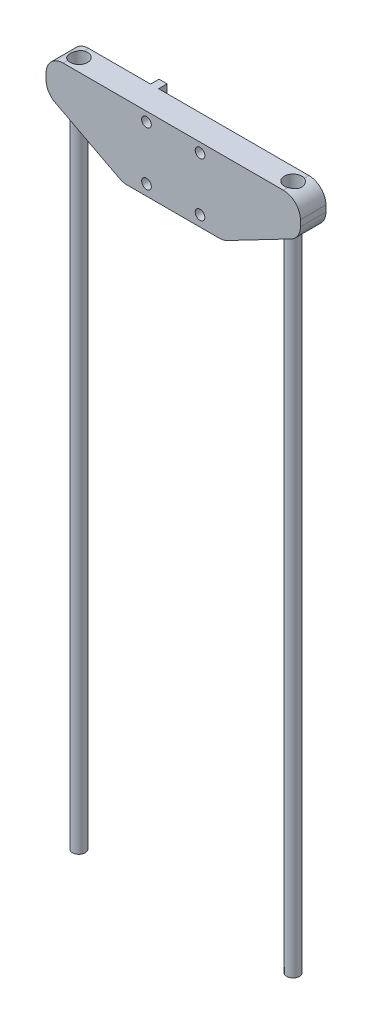
SolidWorks part; units mm, degrees
other "Markup2"
sketch "Sketch8"
other "Markup3"
sketch "Sketch15"
ref_plane "Front Plane" through (0, 0, 0) normal (0, 0, 1) x (1, 0, 0)
ref_plane "Top Plane" through (0, 0, 0) normal (0, 1, 0) x (1, 0, 0)
ref_plane "Right Plane" through (0, 0, 0) normal (1, 0, 0) x (0, 0, -1)
sketch "Sketch2" plane through (0, 0, 0) normal (0, 0, 1) x (1, 0, 0)
  line L0 (-40, 0) -> (-40, -243.6) construction
  line L1 (40, 0) -> (40, -243.6) construction
  line L2 (0, 48.6067) -> (0, -93.2297) construction
  line L3 (-47.5, 12.5) -> (-47.5, 0)
  line L4 (-47.5, 0) -> (-18.75, -15)
  line L5 (-18.75, -15) -> (18.75, -15)
  line L6 (18.75, -15) -> (47.5, 0)
  line L7 (-47.5, 12.5) -> (47.5, 12.5)
  line L8 (47.5, 12.5) -> (47.5, 0)
  line L10 (-42.3812, 0) -> (-37.6188, 0)
  line L11 (-42.3812, 0) -> (-42.3812, -243.6)
  line L12 (-42.3812, -243.6) -> (-37.6187, -243.6)
  line L13 (-37.6188, 0) -> (-37.6187, -243.6)
  line L14 (-10, 9) -> (10, 9) construction
  line L15 (-10, 9) -> (-10, -11) construction
  line L16 (-10, -11) -> (10, -11) construction
  line L17 (10, 9) -> (10, -11) construction
  line L18 (37.6188, -243.6) -> (42.3813, -243.6)
  line L19 (37.6188, -243.6) -> (37.6188, 0)
  line L20 (37.6188, 0) -> (42.3812, 0)
  line L21 (42.3813, -243.6) -> (42.3812, 0)
  dimension "D1" = 80
  dimension "D3" = 4.7625
  dimension "D4" = 20
  dimension "D5" = 20
  dimension "D6" = 228.6
  dimension "12.5" = 12.5
  dimension "D8" = 15
  dimension "D9" = 4
  dimension "D10" = 12.5
  dimension "D11" = 95
  dimension "D12" = 37.5
sketch "Sketch9" plane through (0, 0, 0) normal (0, 1, 0) x (1, 0, 0)
  line L0 (-40, 0) -> (-35, 0) construction
  line L2 (-40, 2.3812) -> (-35, 2.3812)
  line L3 (-40, -2.3812) -> (-35, -2.3812)
  line L4 (0, 20.7896) -> (0, -26.7229) construction
  line L5 (40, 0) -> (35, 0) construction
  line L6 (40, 2.3813) -> (35, 2.3813)
  line L7 (40, -2.3813) -> (35, -2.3813)
  line L8 (-37.5, 2.3812) -> (-37.5, -2.3812) construction
  line L9 (-42.3812, 0) -> (-37.6187, 0) construction
  line L10 (37.5, 2.3813) -> (37.5, -2.3813) construction
  arc A0 (-40, 2.3812) -> (-40, -2.3812) centre (-40, 0) ccw
  arc A1 (-35, -2.3812) -> (-35, 2.3812) centre (-35, 0) ccw
  arc A2 (40, 2.3813) -> (40, -2.3813) centre (40, 0) cw
  arc A3 (35, -2.3813) -> (35, 2.3813) centre (35, 0) cw
  circle A4 centre (-40, 0) radius 1.5
  circle A5 centre (40, 0) radius 1.5
  point P5 (-37.5, 0)
  point P15 (37.5, 0)
  dimension "D1" = 5
  dimension "D3" = 3
  dimension "D2" = 4.7625
sketch "Sketch3" plane through (0, 0, 0) normal (0, 0, 1) x (1, 0, 0)
  line L0 (-47.5, 12.5) -> (-47.5, 0) construction
  line L1 (-47.5, 0) -> (-18.75, -15) construction
  line L2 (-18.75, -15) -> (18.75, -15) construction
  line L3 (18.75, -15) -> (47.5, 0) construction
  line L4 (47.5, 12.5) -> (47.5, 0) construction
  line L5 (-47.5, 12.5) -> (47.5, 12.5) construction
  line L6 (-47.5, 12.5) -> (-47.5, 0)
  line L7 (-47.5, 0) -> (-18.75, -15)
  line L8 (-18.75, -15) -> (18.75, -15)
  line L9 (18.75, -15) -> (47.5, 0)
  line L10 (47.5, 12.5) -> (47.5, 0)
  line L11 (-47.5, 12.5) -> (47.5, 12.5)
extrude "Boss-Extrude1" add sketch "Sketch3" along normal mid plane 9.525
sketch "Sketch10" plane through (0, 0, 0) normal (0, 1, 0) x (1, 0, 0)
  line L0 (40, 2.3813) -> (35, 2.3813) construction
  line L1 (40, -2.3813) -> (35, -2.3813) construction
  line L2 (-40, 2.3812) -> (-35, 2.3812) construction
  line L3 (-40, -2.3812) -> (-35, -2.3812) construction
  line L4 (40, 2.3813) -> (35, 2.3813)
  line L5 (40, -2.3813) -> (35, -2.3813)
  line L6 (-40, 2.3812) -> (-35, 2.3812)
  line L7 (-40, -2.3812) -> (-35, -2.3812)
  arc A0 (35, 2.3813) -> (35, -2.3813) centre (35, 0) ccw construction
  arc A1 (40, -2.3813) -> (40, 2.3813) centre (40, 0) ccw construction
  arc A2 (-35, -2.3812) -> (-35, 2.3812) centre (-35, 0) ccw construction
  arc A3 (-40, 2.3812) -> (-40, -2.3812) centre (-40, 0) ccw construction
  arc A4 (35, 2.3813) -> (35, -2.3813) centre (35, 0) ccw
  arc A5 (40, -2.3813) -> (40, 2.3813) centre (40, 0) ccw
  arc A6 (-35, -2.3812) -> (-35, 2.3812) centre (-35, 0) ccw
  arc A7 (-40, 2.3812) -> (-40, -2.3812) centre (-40, 0) ccw
extrude "Cut-Extrude1" cut sketch "Sketch10" against normal blind 10
sketch "Sketch4" plane through (0, 0, 0) normal (0, 0, 1) x (1, 0, 0)
  line L0 (40, 0) -> (40, -243.6) construction
  line L1 (-40, 0) -> (-40, -243.6) construction
  line L2 (-42.3812, 0) -> (-42.3812, -243.6) construction
  line L3 (-42.3812, -243.6) -> (-37.6187, -243.6) construction
  line L4 (-37.6188, 0) -> (-37.6187, -243.6) construction
  line L5 (-42.3812, 0) -> (-37.6188, 0) construction
  line L6 (40, 0) -> (40, -243.6)
  line L7 (-40, 0) -> (-40, -243.6)
  line L8 (-42.3812, 0) -> (-42.3812, -243.6)
  line L9 (-42.3812, -243.6) -> (-40, -243.6)
  line L10 (-37.6188, 0) -> (-37.6187, -243.6) construction
  line L11 (-42.3812, 0) -> (-40, 0)
  line L12 (-40, -243.6) -> (-40, -275.6996) construction
  line L13 (-40, -243.6) -> (-37.6187, -243.6) construction
  line L14 (-40, 0) -> (-37.6188, 0) construction
  line L15 (40, -243.6) -> (40, -281.3243) construction
  line L16 (37.6188, -243.6) -> (42.3813, -243.6)
  line L17 (37.6188, -243.6) -> (37.6188, 0)
  line L18 (37.6188, 0) -> (42.3812, 0)
  line L19 (42.3813, -243.6) -> (42.3812, 0)
  line L20 (37.6188, -247.4505) -> (40, -247.4505) construction
revolve "Revolve1" add sketch "Sketch4" angle 360 about L12 region at (-41.1906, -121.8, 0)
revolve "Revolve2" add sketch "Sketch4<3>" angle 360 about L15 region at (38.8094, -121.8, 0)
sketch "Sketch4<3>" plane through (0, 0, 0) normal (0, 0, 1) x (1, 0, 0) same geometry as "Sketch4"
hole_wizard "M3 Clearance Hole1" positions "Sketch5" profile "Sketch6" hole size "M3" standard "ANSI Metric" end condition through all
sketch "Sketch5" plane through (0, 0, 4.7625) normal (0, 0, 1) x (1, 0, 0)
  point P0 (-10, 9)
  point P3 (-10, -11)
  point P6 (10, -11)
  point P9 (10, 9)
sketch "Sketch6" plane through (-10, 9, 4.7625) normal (1, 0, 0) x (0, -1, 0)
  line L0 (0, 0) -> (0, 9.525)
  line L1 (0, 9.525) -> (1.8, 9.525)
  line L2 (1.8, 9.525) -> (1.8, 0)
  line L5 (1.8, 0) -> (0, 0)
  line L11 (0, -6.35) -> (0, 107.95) construction
  dimension "Thru Hole Dia." = 3.6
  dimension "Thru Hole Depth" = 9.525
hole_wizard "CBORE for M3 SHCS2" positions "Sketch11" profile "Sketch12" counterbore size "M3" standard "ANSI Metric" end condition through all
sketch "Sketch11" plane through (0, 12.5, 0) normal (0, 1, 0) x (1, 0, 0)
  point P0 (-40, 0)
  point P3 (40, 0)
sketch "Sketch12" plane through (-40, 12.5, 0) normal (1, 0, 0) x (0, 0, 1)
  line L0 (0, 0) -> (0, 256.1)
  line L1 (0, 256.1) -> (1.8, 256.1)
  line L3 (1.8, 256.1) -> (1.8, 9.5)
  line L4 (1.8, 9.5) -> (3.25, 9.5)
  line L5 (3.25, 9.5) -> (3.25, 0)
  line L7 (3.25, 0) -> (0, 0)
  line L11 (0, -6.35) -> (0, 107.95) construction
  dimension "Thru Hole Dia." = 3.6
  dimension "Thru Hole Depth" = 256.1
  dimension "C'Bore Dia." = 6.5
  dimension "C'Bore Depth" = 9.5
hole_wizard "M3x0.5 Tapped Hole1" positions "Sketch13" profile "Sketch14" tap size "M3x0.5" standard "ANSI Metric"
sketch "Sketch13" plane through (0, 0, 0) normal (0, 1, 0) x (1, 0, 0)
  point P0 (-40, 0)
  point P3 (40, 0)
sketch "Sketch14" plane through (-40, 0, 0) normal (1, 0, 0) x (0, 0, 1)
  line L0 (0, 0) -> (0, 8.2511)
  line L1 (0, 8.2511) -> (1.25, 7.5)
  line L2 (1.25, 7.5) -> (1.25, 0)
  line L5 (1.25, 0) -> (0, 0)
  line L10 (0, 8.2511) -> (-1.25, 7.5) construction
  line L11 (0, -6.35) -> (0, 107.95) construction
  dimension "Tap Drill Dia." = 2.5
  dimension "Tap Drill Depth" = 7.5
  dimension "Drill Angle" = 118
fillet "Fillet1" radius 6.35 6 edges at (-18.75, -15, 0) (18.75, -15, 0) (47.5, 0, 0) (47.5, 12.5, 0) (-47.5, 12.5, 0) (-47.5, 0, 0)
sketch "Sketch16" plane through (0, 0, -4.7625) normal (0, 0, -1) x (-1, 0, 0)
  line L0 (-41.15, 12.5) -> (41.15, 12.5) construction
  line L1 (18, -12) -> (15, -12)
  line L2 (18, -12) -> (18, 12.5)
  line L3 (18, 12.5) -> (15, 12.5)
  line L4 (15, -12) -> (15, 12.5)
  line L6 (17.1931, -15) -> (-17.1931, -15) construction
  circle A0 centre (10, -11) radius 1.8 construction
  dimension "D1" = 5
  dimension "D2" = 3
  dimension "D3" = 3
extrude "Boss-Extrude2" add sketch "Sketch16" along normal blind 3.175
